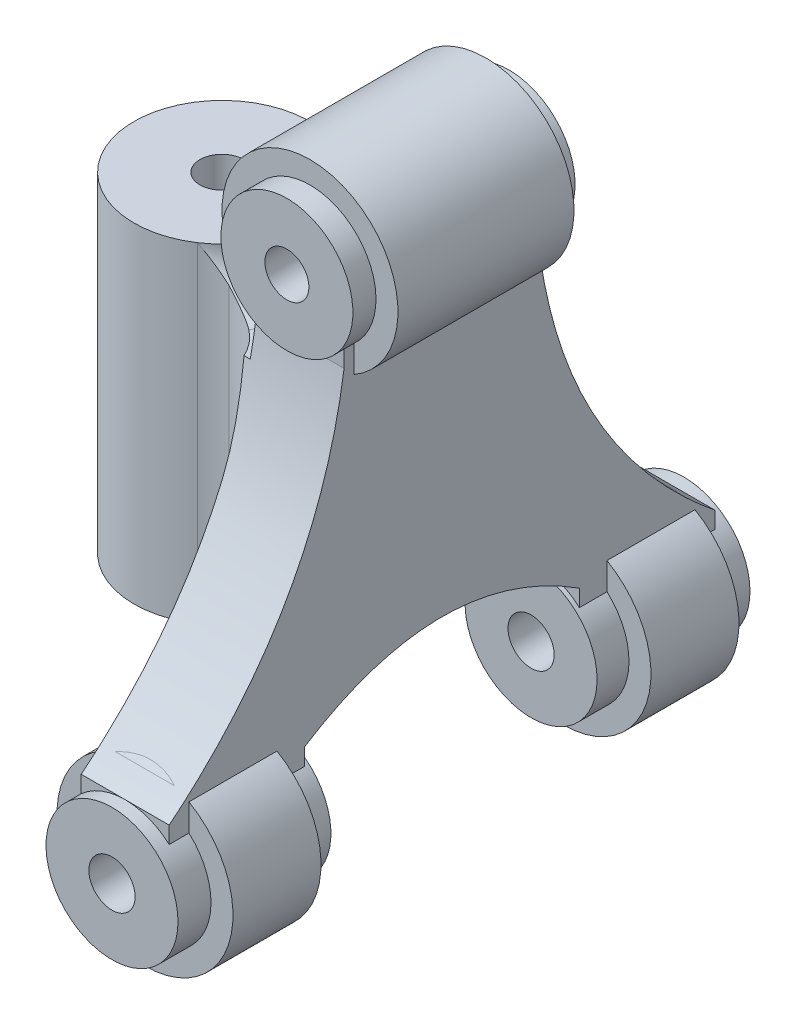
SolidWorks part; units mm, degrees
ref_plane "Спереди" through (0, 0, 0) normal (0, 0, 1) x (1, 0, 0)
ref_plane "Сверху" through (0, 0, 0) normal (0, 1, 0) x (1, 0, 0)
ref_plane "Справа" through (0, 0, 0) normal (1, 0, 0) x (0, 0, -1)
sketch "Эскиз1" plane through (0, 0, 0) normal (0, 1, 0) x (1, 0, 0)
  circle A0 centre (0, 0) radius 4
  circle A1 centre (0, 0) radius 1
  dimension "D1" = 8
  dimension "D2" = 2
extrude "Бобышка-Вытянуть1" add sketch "Эскиз1" along normal blind 15
ref_plane "Плоскость1" through (4, 0, 0) normal (1, 0, 0) x (0, 0, -1)
sketch "Эскиз10" plane through (0, 0, 0) normal (0, 0, 1) x (1, 0, 0)
  line L0 (8, 38.4804) -> (8, -11.0207) construction
  line L1 (-4, 7.5) -> (4, 7.5) construction
  line L2 (-4, 15) -> (-4, 0) construction
  line L3 (4, 0) -> (4, 15) construction
  line L4 (4, 15) -> (-4, 15) construction
  circle A0 centre (8, 17.5) radius 1
  circle A1 centre (8, 17.5) radius 3
  circle A2 centre (8, -2.5) radius 1.05
  circle A3 centre (8, -2.5) radius 3
  point P14 (0, 15)
  dimension "D1" = 2
  dimension "D2" = 6
  dimension "D5" = 2.1
  dimension "D3" = 20
  dimension "D4" = 8
extrude "Бобышка-Вытянуть8" add sketch "Эскиз10" along normal mid plane 26 separate body
sketch "Эскиз12" plane through (0, 15, 0) normal (0, 1, 0) x (1, 0, 0)
  line L0 (5, 13) -> (5, -13) construction
  line L1 (5, 5.05) -> (11, 5.05)
  line L2 (5, 5.05) -> (5, -5.05)
  line L3 (5, -5.05) -> (11, -5.05)
  line L4 (11, 5.05) -> (11, -5.05)
  line L5 (11, -13) -> (11, 13) construction
  line L6 (0, 0) -> (17.937, 0) construction
  line L8 (5, 13) -> (11, 13)
  line L9 (5, 13) -> (5, 5.05)
  line L10 (5, 5.05) -> (11, 5.05)
  line L11 (11, 13) -> (11, 5.05)
  line L12 (5, -5.05) -> (11, -5.05)
  line L13 (5, -5.05) -> (5, -13)
  line L14 (5, -13) -> (11, -13)
  line L15 (11, -5.05) -> (11, -13)
  dimension "D1" = 10.1
extrude "Вырез-Вытянуть2" cut sketch "Эскиз12" against normal blind 2 and the other way blind 6 contours L15 L3 L13 L14 | L11 L8 L9 L1
sketch "Эскиз13" plane through (0, 0, 0) normal (0, 1, 0) x (1, 0, 0)
  line L0 (8, 13) -> (8, -13) construction
  line L1 (11, 13) -> (5, 13) construction
  line L2 (5, -13) -> (11, -13) construction
  line L4 (11, -6.05) -> (5, -6.05)
  line L5 (11, -6.05) -> (11, 6.05)
  line L6 (11, 6.05) -> (5, 6.05)
  line L7 (5, -6.05) -> (5, 6.05)
  line L8 (11, -6.05) -> (5, 6.05) construction
  line L9 (11, 6.05) -> (5, -6.05) construction
  point P6 (8, 0)
  dimension "D1" = 6
  dimension "D2" = 12.1
extrude "Вырез-Вытянуть3" cut sketch "Эскиз13" against normal blind 6 and the other way blind 2
sketch "Эскиз15" plane through (4, 0, 0) normal (1, 0, 0) x (0, 0, -1)
  line L0 (0, -2.5888) -> (0, 21.5777) construction
  line L1 (-3, 13) -> (3, 13)
  line L2 (-3, 13) -> (-3, 3)
  line L3 (-3, 3) -> (3, 3)
  line L4 (3, 13) -> (3, 3)
  line L5 (-4, 0) -> (4, 0) construction
  dimension "D1" = 10
  dimension "D2" = 6
  dimension "D3" = 3
extrude "Бобышка-Вытянуть9" add sketch "Эскиз15" along normal blind 6 and the other way up to next
ref_plane "Плоскость2" through (8, 0, 0) normal (1, 0, 0) x (0, 0, -1)
sketch "Эскиз16" plane through (8, 0, 0) normal (1, 0, 0) x (0, 0, -1)
  line L0 (0, 21.1124) -> (0, -7.3755) construction
  line L1 (-5.05, 14.5) -> (5.05, 14.5) construction
  line L2 (-6.05, 0.5) -> (-13, 0.5) construction
  line L3 (13, 0.5) -> (6.05, 0.5) construction
  line L4 (-6.05, -5.5) -> (-6.05, 0.5) construction
  line L5 (-13, 0.5) -> (-13, -5.5) construction
  line L6 (-5.05, 20.5) -> (-5.05, 14.5) construction
  line L12 (-4.45, 14.5) -> (-4.45, 16.4)
  line L13 (-4.45, 16.4) -> (4.45, 16.4)
  line L16 (-12.4, 0.5) -> (-12.4, -1.4)
  line L17 (-12.4, -1.4) -> (-6.25, -1.4)
  line L18 (-6.25, 0.5) -> (-6.25, -1.4)
  line L20 (6.25, 0.5) -> (6.25, -1.4)
  line L21 (6.25, -1.4) -> (12.4, -1.4)
  line L22 (12.4, 0.5) -> (12.4, -1.4)
  line L24 (4.45, 16.4) -> (4.45, 14.5)
  spline S0 degree 2 poles (-4.45, 14.5) (-5.69, 5.9572) (-12.4, 0.5) knots 0 0 0 1 1 1
  spline S1 degree 2 poles (-6.25, 0.5) (0, 4.5) (6.25, 0.5) knots 0 0 0 1 1 1
  spline S2 degree 2 poles (4.45, 14.5) (5.69, 5.9572) (12.4, 0.5) knots 0 0 0 1 1 1
  dimension "D1" = 0.2
  dimension "D2" = 0.6
  dimension "D3" = 0.6
  dimension "D4" = 2
  dimension "D5" = 1.9
  dimension "D6" = 1.9
extrude "Бобышка-Вытянуть10" add sketch "Эскиз16" along normal mid plane 4
fillet "Скругление1" radius 2 4 edges at (4, 3, 0) (2.6458, 8, -3) (2.6458, 8, 3) (4, 13, 0)
sketch "Эскиз17" plane through (0, 0, 0) normal (0, 0, 1) x (1, 0, 0)
  circle A0 centre (8, 17.5) radius 3
  circle A1 centre (8, 17.5) radius 4
  dimension "D1" = 8
extrude "Бобышка-Вытянуть11" add sketch "Эскиз17" along normal mid plane 8
ref_plane "Плоскость3" through (0, 0, 9.5) normal (0, 0, 1) x (1, 0, 0)
sketch "Эскиз18" plane through (0, 0, 9.5) normal (0, 0, 1) x (1, 0, 0)
  circle A0 centre (8, -2.5) radius 3
  circle A1 centre (8, -2.5) radius 4
  circle A2 centre (8, -2.5) radius 3 construction
  dimension "D1" = 8
extrude "Бобышка-Вытянуть12" add sketch "Эскиз18" along normal mid plane 4
sketch "Эскиз19" plane through (0, 0, 0) normal (1, 0, 0) x (0, 0, -1)
  line L0 (-11.5, 1.2678) -> (-11.5, 1.5)
  line L1 (-11.5, 1.5) -> (-11.2444, 1.5)
  parabola Q1 (-4.45, 14.5) -> (-12.4, 0.5) focus (-16.0155, 11.8491) apex (-7.0287, 6.7795) construction
  parabola Q2 (-4.45, 14.5) -> (-12.4, 0.5) focus (-16.0155, 11.8491) apex (-7.0287, 6.7795)
extrude "Вырез-Вытянуть4" cut sketch "Эскиз19" against normal through all both and the other way through all contours Q2 L1 L0
mirror "Зеркальное отражение1" about plane through (0, 0, 0) normal (0, 0, 1) of "Бобышка-Вытянуть12", "Вырез-Вытянуть4"
fillet "Скругление2" radius 3 2 edges at (6, 8, -3) (6, 8, 3)
